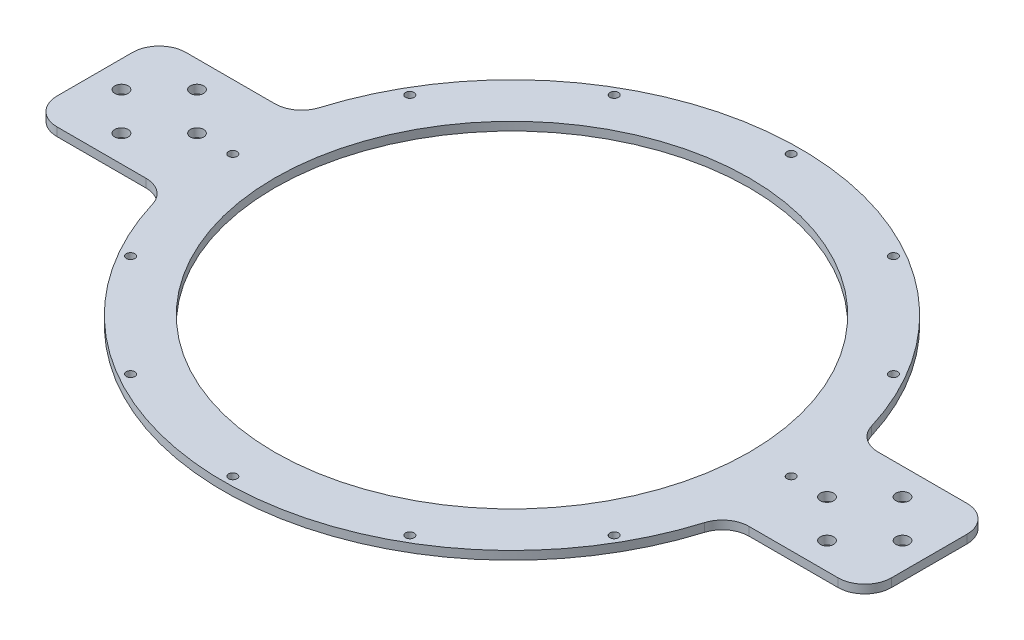
SolidWorks part; units mm, degrees
material "AISI 304"
ref_plane "Front Plane" through (0, 0, 0) normal (0, 0, 1) x (1, 0, 0)
ref_plane "Top Plane" through (0, 0, 0) normal (0, 1, 0) x (1, 0, 0)
ref_plane "Right Plane" through (0, 0, 0) normal (1, 0, 0) x (0, 0, -1)
sketch "Sketch1" plane through (0, 0, 0) normal (0, 1, 0) x (1, 0, 0)
  circle A0 centre (0, 0) radius 88.9
  circle A1 centre (0, 0) radius 107.95
  dimension "D1" = 177.8
  dimension "D2" = 215.9
extrude "Boss-Extrude1" add sketch "Sketch1" along normal blind 3.175
hole_wizard "M3 Clearance Hole1" positions "Sketch9" profile "Sketch10" hole size "M3" standard "ANSI Metric" end condition through all
sketch "Sketch9" plane through (0, 3.175, 0) normal (0, 1, 0) x (1, 0, 0)
  line L0 (0, 0) -> (0, 104.55) construction
  point P2 (0, 104.55)
  dimension "D1" = 104.55
sketch "Sketch10" plane through (0, 3.175, -104.55) normal (1, 0, 0) x (0, 0, 1)
  line L0 (0, 0) -> (0, 3.175)
  line L1 (0, 3.175) -> (1.6, 3.175)
  line L2 (1.6, 3.175) -> (1.6, 0)
  line L5 (1.6, 0) -> (0, 0)
  line L11 (0, -6.35) -> (0, 107.95) construction
  dimension "Thru Hole Dia." = 3.2
  dimension "Thru Hole Depth" = 3.175
pattern_circular "CirPattern1" count 12 over 360 about axis through (0, 3.175, 0) along (0, -1, 0) of "M3 Clearance Hole1"
sketch "Sketch2" plane through (0, 0, 0) normal (0, 1, 0) x (1, 0, 0)
  line L0 (-156.2343, 24.1421) -> (-105.2158, 24.1421)
  line L1 (-105.2158, -24.1421) -> (-156.2343, -24.1421)
  line L2 (-156.2343, -24.1421) -> (-156.2343, 24.1421)
  line L3 (-156.2343, 0) -> (0, 0) construction
  line L4 (-146.2343, 0) -> (-132.0921, 14.1421) construction
  line L5 (-132.0921, 14.1421) -> (-117.95, 0) construction
  line L6 (-117.95, 0) -> (-132.0921, -14.1421) construction
  line L7 (-132.0921, -14.1421) -> (-146.2343, 0) construction
  circle A0 centre (0, 0) radius 107.95 construction
  circle A1 centre (0, 0) radius 107.95 construction
  arc A2 (-105.2158, 24.1421) -> (-105.2158, -24.1421) centre (0, 0) ccw
  point P11 (-107.95, 0)
  point P14 (-126.8264, -11.9353)
  point P15 (0, 0)
  dimension "D1" = 20
  dimension "D2" = 10
  dimension "D3" = 10
  dimension "D4" = 10
extrude "Boss-Extrude2" add sketch "Sketch2" along normal up to surface (3.175 mm away) up to face at (-52.275, 3.175, -88.943)
hole_wizard "#10 Clearance Hole3" positions "Sketch7" profile "Sketch8" hole size "#10" standard "ANSI Inch" end condition through all
sketch "Sketch7" plane through (0, 3.175, 0) normal (0, 1, 0) x (1, 0, 0)
  line L0 (-117.95, 0) -> (-132.0921, -14.1421) construction
  line L1 (-132.0921, -14.1421) -> (-146.2343, 0) construction
  line L2 (-146.2343, 0) -> (-132.0921, 14.1421) construction
  line L3 (-132.0921, 14.1421) -> (-117.95, 0) construction
  line L4 (-117.95, 0) -> (-132.0921, -14.1421) construction
  line L5 (-132.0921, -14.1421) -> (-146.2343, 0) construction
  line L6 (-146.2343, 0) -> (-132.0921, 14.1421) construction
  line L7 (-132.0921, 14.1421) -> (-117.95, 0) construction
  point P0 (-132.0921, -14.1421)
  point P2 (-117.95, 0)
  point P4 (-132.0921, 14.1421)
  point P6 (-146.2343, 0)
  point P17 (-132.0921, 14.1421)
  point P18 (-117.95, 0)
  point P19 (-132.0921, -14.1421)
  point P20 (-146.2343, 0)
sketch "Sketch8" plane through (-132.0921, 3.175, 14.1421) normal (1, 0, 0) x (0, 0, 1)
  line L0 (0, 0) -> (0, 3.175)
  line L1 (0, 3.175) -> (2.4892, 3.175)
  line L2 (2.4892, 3.175) -> (2.4892, 0)
  line L5 (2.4892, 0) -> (0, 0)
  line L11 (0, -6.35) -> (0, 107.95) construction
  dimension "Thru Hole Dia." = 4.9784
  dimension "Thru Hole Depth" = 3.175
fillet "Fillet1" radius 10 4 edges at (-105.2158, 1.5875, -24.1421) (-156.2343, 1.5875, -24.1421) (-156.2343, 1.5875, 24.1421) (-105.2158, 1.5875, 24.1421)
mirror "Mirror1" about plane through (0, 0, 0) normal (1, 0, 0) of "#10 Clearance Hole3", "Fillet1", "Boss-Extrude2"
